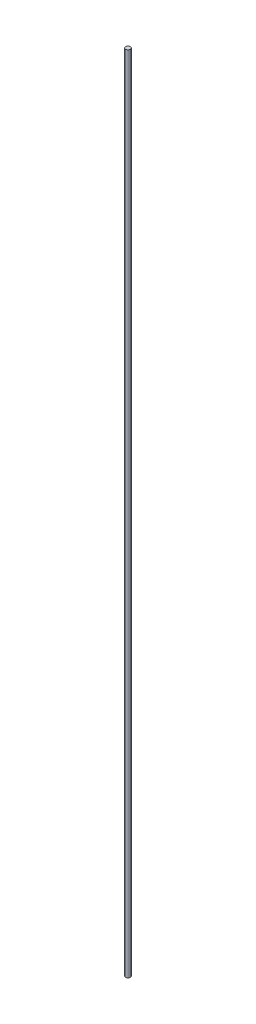
SolidWorks part; units mm, degrees
ref_plane "Спереди" through (0, 0, 0) normal (0, 0, 1) x (1, 0, 0)
ref_plane "Сверху" through (0, 0, 0) normal (0, 1, 0) x (1, 0, 0)
ref_plane "Справа" through (0, 0, 0) normal (1, 0, 0) x (0, 0, -1)
sketch "Эскиз2" plane through (0, 0, 0) normal (0, 0, 1) x (1, 0, 0)
  line L0 (0, 347.7) -> (-5, 347.7) construction
  line L5 (-2.5, 347.7) -> (0, 347.7)
  line L6 (-2.5, 347.7) -> (-2.5, -511.36)
  line L7 (-2.5, -511.36) -> (0, -511.36)
  line L8 (0, 347.7) -> (0, -511.36)
  line L9 (-2.5, 347.7) -> (0, -511.36) construction
  line L10 (-2.5, -511.36) -> (0, 347.7) construction
  line L11 (-5, -511.36) -> (0, -511.36) construction
  point P0 (-1.25, -81.83)
  point P12 (0, 0)
  dimension "D1" = 2.5
revolve "Повернуть1" add sketch "Эскиз2" angle 360 about L6
equation "\"Ширина груза\"= 420"
equation "\"Глубина груза\"= 490"
equation "\"Высота груза\"= 297"
equation "\"Ширина ячейки\"= \"Ширина груза\" + 10"
equation "\"Глубина ячейки\"= \"Глубина груза\" + 10"
equation "\"Высота ячейки\"= \"Высота груза\" + 10 + 13"
equation "\"Колво ячеек ширина\"= 2"
equation "\"Колво ячеек высота\"= 2"
equation "\"Толщина стенки\"= 10"
equation "\"Крепление дверцы\"= 5"
equation "\"Ширина рейки\"= \"Толщина шестерни\""
equation "\"Высота рейки\"= 20"
equation "\"Высота пола\"= 20"
equation "\"Колво полозьев\"= 5"
equation "\"Отступ рейки\"= 20"
equation "\"Глубина каретки\"= \"Глубина ячейки\" + 30 + \"Мотор Y высота корпуса\" + 20"
equation "\"Длинна рейки\"= ( \"Ширина ячейки\" + \"Толщина стенки\" + \"Крепление дверцы\" ) * \"Колво ячеек ширина\" + \"Ширина ячейки выгрузки\" * \"Колво выгрузки\" + \"Толщина стенки\""
equation "\"Отступ шпильки\"= 20"
equation "\"Диаметр шпильки\"= 5"
equation "\"Длинна шпильки\"= ( \"Высота ячейки\" + \"Толщина стенки\" + \"Высота пола\" ) * \"Колво ячеек высота\" + ( \"Толщина стенки\" + \"Отступ рейки\" ) * 2 "
equation "\"D1@Эскиз2\"= \"Диаметр шпильки\" / 2"
equation "\"Ширина пластины\"= 50  "
equation "\"Высота зона выгрузки\"= \"Высота ячейки\" * 2 + \"Толщина стенки\" * 2"
equation "\"Колво выгрузки\"= 1"
equation "\"Отступ крепления мотора фиксации\" = 30"
equation "\"Мотор X ширина корпуса\"= 42.3"
equation "\"Мотор X высота корпуса\"= 42.3"
equation "\"Мотор X длина корпуса\"= 40"
equation "\"Мотор X вылет вала\"= 19.8"
equation "\"Мотор Y ширина корпуса\"= 42.3"
equation "\"Мотор Y высота корпуса\"= 42.3"
equation "\"Мотор Y длина корпуса\"= 48"
equation "\"Мотор Y вылет вала\"= 30"
equation "\"Мотор Z ширина корпуса\"= 42"
equation "\"Мотор Z высота корпуса\"= 42"
equation "\"Мотор Z длина корпуса\"= 40"
equation "\"Мотор Z вылет вала\"= 23"
equation "\"Мотор диаметр вала ПРЕДВ\"= 5"
equation "\"Мотор шаг крепления ПРЕДВ\"= 31"
equation "\"Мотор диаметр отверстий ПРЕДВ\"= 3"
equation "\"Мотор глубина отверстий ПРЕДВ\"= 4.5"
equation "\"Мотор диаметр буртика ПРЕДВ\"= 22"
equation "\"Мотор высота буртика ПРЕДВ\"= 2"
equation "\"Мотор диаметр шкива ПРЕДВ\"= 16"
equation "\"Мотор длина шкива ПРЕДВ\"= 12"
equation "\"Мотор отступ шкива ПРЕДВ\"= 5"
equation "\"Мотор X шаг градусов\"= 1.8"
equation "\"Мотор X ток А\"= 1.5"
equation "\"Мотор X сопротивление Ом\"= 1.3"
equation "\"Мотор X индуктивность мГн\"= 2"
equation "\"Мотор Y шаг градусов\"= 1.8"
equation "\"Мотор Y ток А\"= 2.2"
equation "\"Мотор Y сопротивление Ом\"= 0.9"
equation "\"Мотор Y индуктивность мГн\"= 2"
equation "\"Мотор Z шаг градусов\"= 1.8"
equation "\"Мотор Z ток А\"= 1"
equation "\"Мотор Z сопротивление Ом\"= 4"
equation "\"Мотор Z индуктивность мГн\"= 8"
equation "\"Мотор Y диаметр ротора\"= 25.78"
equation "\"Ширина ячейки выгрузки\"= \"Ширина ячейки\" + \"Толщина стенки\" + \"Отступ крепления мотора фиксации\"*2"
